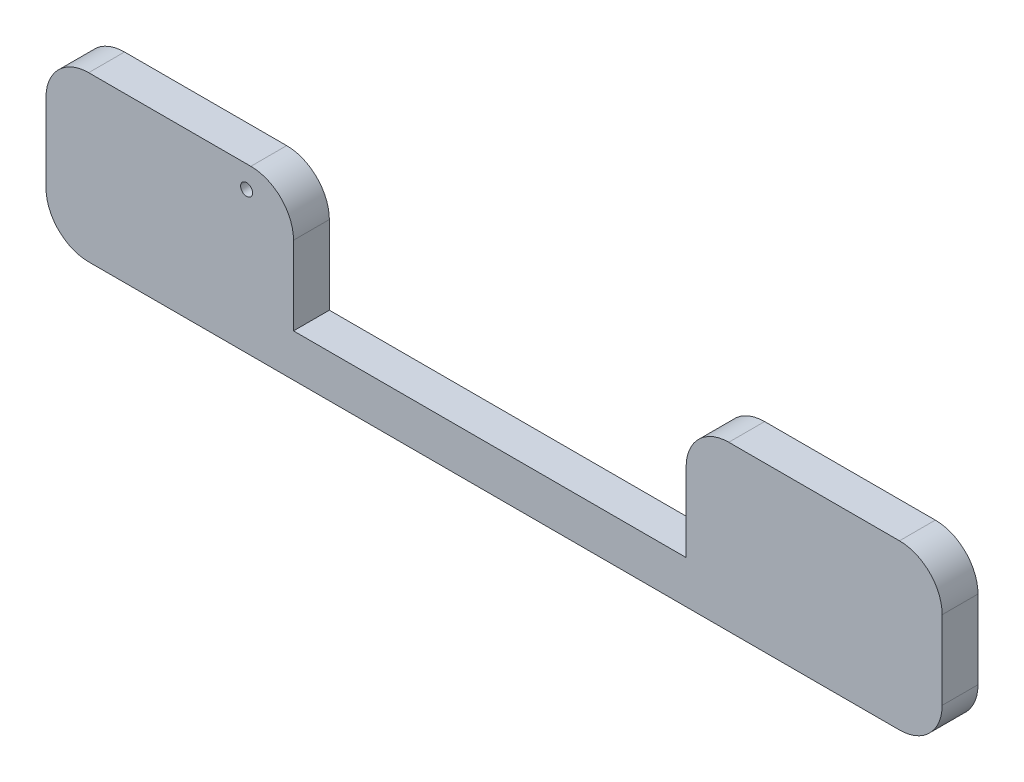
SolidWorks part; units mm, degrees
ref_plane "Front Plane" through (0, 0, 0) normal (0, 0, 1) x (1, 0, 0)
ref_plane "Top Plane" through (0, 0, 0) normal (0, 1, 0) x (1, 0, 0)
ref_plane "Right Plane" through (0, 0, 0) normal (1, 0, 0) x (0, 0, -1)
sketch "Sketch1" plane through (0, 0, 0) normal (0, 0, 1) x (1, 0, 0)
  line L1 (-85.0624, -35.0708) -> (48.2876, -35.0708)
  line L2 (-85.0624, -35.0708) -> (-85.0624, -59.4548)
  line L3 (-85.0624, -59.4548) -> (48.2876, -59.4548)
  line L4 (48.2876, -35.0708) -> (48.2876, -59.4548)
  dimension "D1" = 133.35
  dimension "D2" = 24.384
extrude "Boss-Extrude1" add sketch "Sketch1" along normal blind 5.334
sketch "Sketch3" plane through (0, 0, 5.334) normal (0, 0, 1) x (1, 0, 0)
  line L0 (48.2876, -35.0708) -> (-85.0624, -35.0708) construction
  line L1 (-48.2324, -35.0708) -> (10.1876, -35.0708)
  line L2 (-48.2324, -35.0708) -> (-48.2324, -53.1048)
  line L3 (-48.2324, -53.1048) -> (10.1876, -53.1048)
  line L4 (10.1876, -35.0708) -> (10.1876, -53.1048)
  line L5 (48.2876, -59.4548) -> (48.2876, -35.0708) construction
  dimension "D1" = 38.1
  dimension "D2" = 58.42
  dimension "D3" = 18.034
extrude "Cut-Extrude1" cut sketch "Sketch3" against normal through all
fillet "Fillet1" radius 6.35 6 edges at (-85.0624, -35.0708, 2.667) (-48.2324, -35.0708, 2.667) (10.1876, -35.0708, 2.667) (48.2876, -35.0708, 2.667) (48.2876, -59.4548, 2.667) (-85.0624, -59.4548, 2.667)
sketch "Sketch4" plane through (0, 0, 5.334) normal (0, 0, 1) x (1, 0, 0)
  line L1 (-85.0624, -47.2628) -> (-69.9279, -47.2628) construction
  line L2 (-85.0624, -41.4208) -> (-85.0624, -53.1048) construction
  line L3 (-66.6474, -35.0708) -> (-66.6474, -42.5901) construction
  line L4 (-54.5824, -35.0708) -> (-78.7124, -35.0708) construction
  circle A0 centre (-55.2174, -38.3728) radius 0.889
  dimension "D1" = 1.778
  dimension "D2" = 8.89
  dimension "D3" = 11.43
extrude "Cut-Extrude2" cut sketch "Sketch4" against normal through all
equation "\"MDF\"= .21in"
equation "\"Foamcore\"= .13in"
equation "\"Gmaterial\"= \"MDF\""
equation "\"D2@Sketch1\"=\"MDF\"+.25+.5"
equation "\"D1@Boss-Extrude1\"=\"MDF\""
equation "\"D3@Sketch3\"=\"MDF\"+.5"
